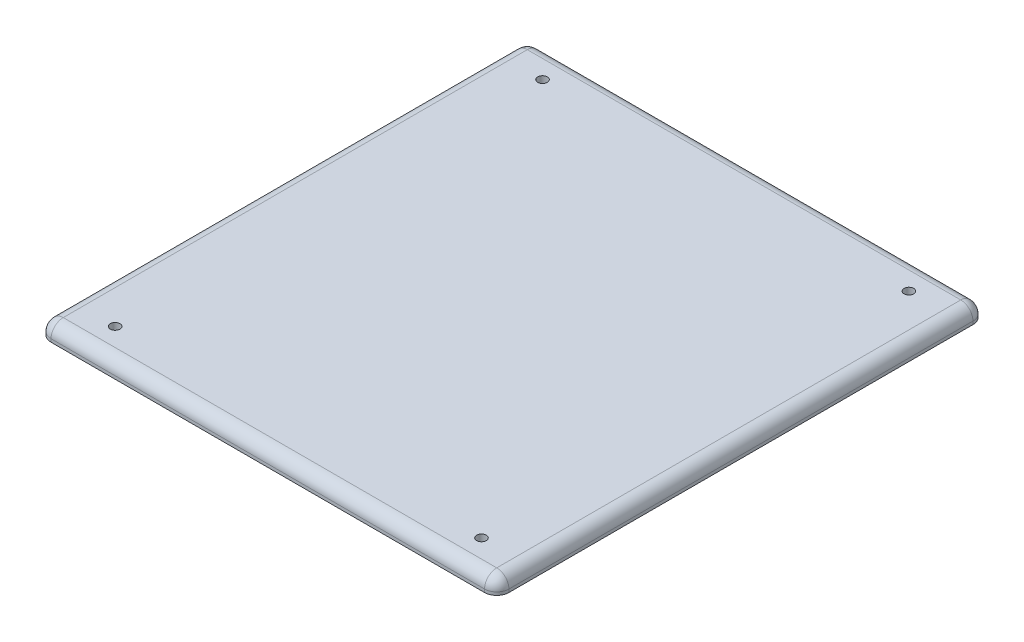
SolidWorks part; units mm, degrees
ref_plane "Front Plane" through (0, 0, 0) normal (0, 0, 1) x (1, 0, 0)
ref_plane "Top Plane" through (0, 0, 0) normal (0, 1, 0) x (1, 0, 0)
ref_plane "Right Plane" through (0, 0, 0) normal (1, 0, 0) x (0, 0, -1)
sketch "Sketch1" plane through (0, 0, 0) normal (0, 1, 0) x (1, 0, 0)
  line L1 (47.625, -50.8) -> (-47.625, -50.8)
  line L2 (47.625, -50.8) -> (47.625, 50.8)
  line L3 (47.625, 50.8) -> (-47.625, 50.8)
  line L4 (-47.625, -50.8) -> (-47.625, 50.8)
  line L5 (47.625, -50.8) -> (-47.625, 50.8) construction
  line L6 (47.625, 50.8) -> (-47.625, -50.8) construction
  point P0 (0, 0)
  dimension "D1" = 95.25
  dimension "D2" = 101.6
extrude "Boss-Extrude1" add sketch "Sketch1" along normal blind 3.175
ref_axis "Axis1" through (0, 3.3337, 0) along (0, -1, 0)
sketch "Sketch5" plane through (0, 3.175, 0) normal (0, 1, 0) x (1, 0, 0)
  line L0 (0, 0) -> (0, -50.8) construction
  line L1 (-47.625, -50.8) -> (47.625, -50.8) construction
  line L2 (-47.625, 50.8) -> (-47.625, -50.8) construction
  circle A0 centre (-38.1, -44.45) radius 0.9995
  circle A1 centre (38.1, -44.45) radius 0.9995
  dimension "D3" = 1.999
  dimension "D1" = 9.525
  dimension "D2" = 6.35
extrude "Cut-Extrude3" cut sketch "Sketch5" against normal blind 3.175
pattern_circular "CirPattern3" count 2 over 360 about axis through (0, 3.3337, 0) along (0, -1, 0) of "Cut-Extrude3"
fillet "Fillet1" radius 2.54 8 edges at (47.625, 3.175, 0) (0, 3.175, 50.8) (-47.625, 3.175, 0) (0, 3.175, -50.8) (-47.625, 1.5875, -50.8) (47.625, 1.5875, -50.8) (47.625, 1.5875, 50.8) (-47.625, 1.5875, 50.8)
chamfer "Chamfer1" distance 1.27 angle 45 4 edges at (38.1, 0, -45.4495) (-38.1, 0, -43.4505) (-38.1, 0, 45.4495) (38.1, 0, 43.4505)
